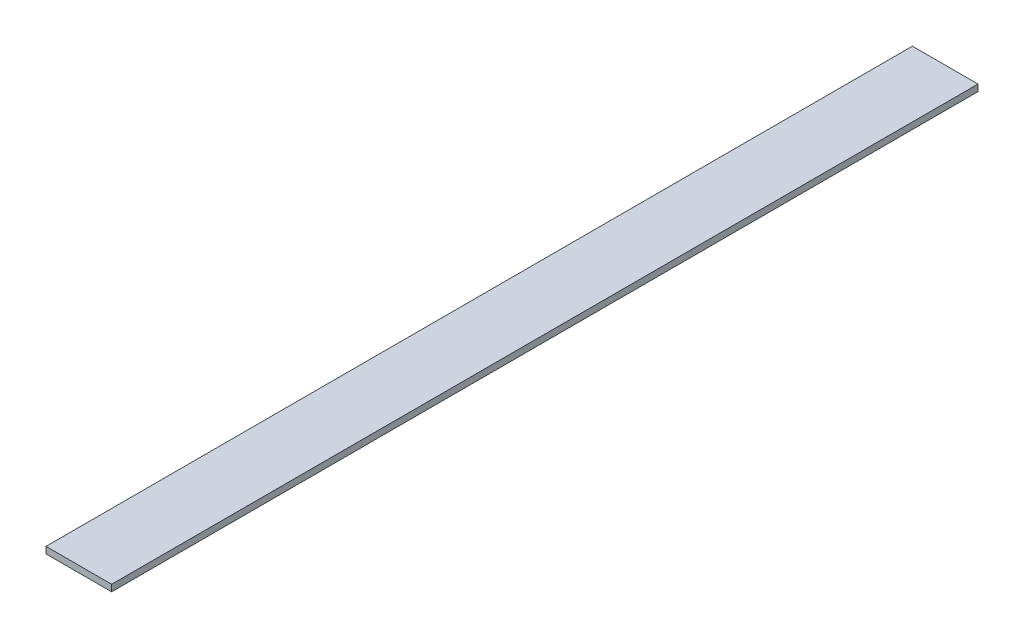
SolidWorks part; units mm, degrees
material "Balsa"
ref_plane "Front Plane" through (0, 0, 0) normal (0, 0, 1) x (1, 0, 0)
ref_plane "Top Plane" through (0, 0, 0) normal (0, 1, 0) x (1, 0, 0)
ref_plane "Right Plane" through (0, 0, 0) normal (1, 0, 0) x (0, 0, -1)
sketch "Sketch1" plane through (0, 0, 0) normal (0, 1, 0) x (1, 0, 0)
  line L1 (-36.5161, 308.7563) -> (-6.5161, 308.7563)
  line L2 (-36.5161, 308.7563) -> (-36.5161, -87.2437)
  line L3 (-36.5161, -87.2437) -> (-6.5161, -87.2437)
  line L4 (-6.5161, 308.7563) -> (-6.5161, -87.2437)
  line L5 (-36.5161, 308.7563) -> (-6.5161, -87.2437) construction
  line L6 (-36.5161, -87.2437) -> (-6.5161, 308.7563) construction
  point P0 (-21.5161, 110.7563)
  dimension "D1" = 396
  dimension "D2" = 30
extrude "Boss-Extrude1" add sketch "Sketch1" along normal blind 3
